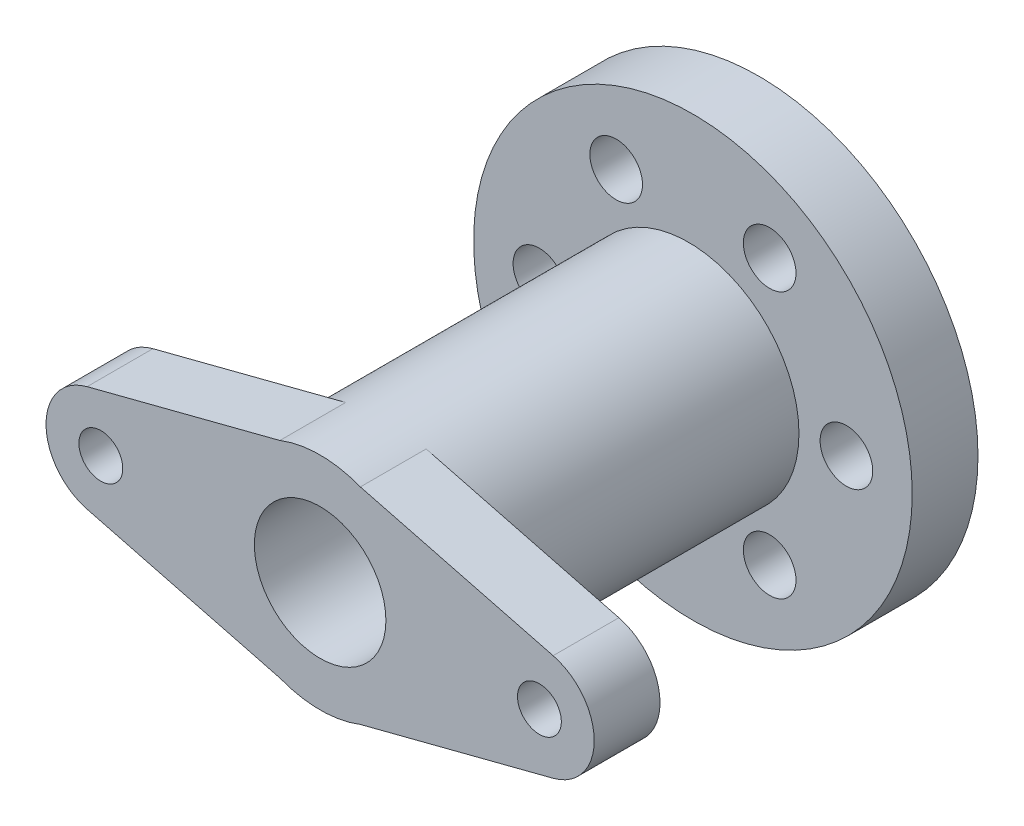
SolidWorks part; units mm, degrees
ref_plane "Front Plane" through (0, 0, 0) normal (0, 0, 1) x (1, 0, 0)
ref_plane "Top Plane" through (0, 0, 0) normal (0, 1, 0) x (1, 0, 0)
ref_plane "Right Plane" through (0, 0, 0) normal (1, 0, 0) x (0, 0, -1)
sketch "Sketch1" plane through (0, 0, 0) normal (0, 0, 1) x (1, 0, 0)
  circle A0 centre (0, 0) radius 50
  circle A1 centre (0, 0) radius 35
  circle A2 centre (-35, 0) radius 6
  circle A3 centre (-17.5, 30.3109) radius 6
  circle A4 centre (0, 0) radius 35
  circle A5 centre (17.5, 30.3109) radius 6
  circle A6 centre (0, 0) radius 35
  circle A7 centre (35, 0) radius 6
  circle A8 centre (0, 0) radius 35
  circle A9 centre (17.5, -30.3109) radius 6
  circle A10 centre (0, 0) radius 35
  circle A11 centre (-17.5, -30.3109) radius 6
  circle A12 centre (0, 0) radius 35
  circle A13 centre (0, 0) radius 15
  point P24 (0, 0)
  dimension "D1" = 100
  dimension "D2" = 70
  dimension "D3" = 12
  dimension "D5" = 30
  dimension "D4" = 6
extrude "Boss-Extrude1" add sketch "Sketch1" along normal blind 15 contours A0 A11 A1 A2 A3 A5 A7 A9 | A11 A1 A9 A7 A5 A3 A2 region at (-48.5858, 0, 0) region at (28.0173, 0, 0)
extrude "Boss-Extrude2" add sketch "Sketch1<3>" along normal blind 85 contours A13 region at (0, 0, 0)
sketch "Sketch1<3>" plane through (0, 0, 0) normal (0, 0, 1) x (1, 0, 0) same geometry as "Sketch1"
sketch "Sketch2" plane through (0, 0, 85) normal (0, 0, 1) x (1, 0, 0)
  line L0 (0, 0) -> (49.3005, 0) construction
  line L1 (-53.125, 12.1031) -> (-6.25, 24.2061)
  line L2 (6.25, 24.2061) -> (53.125, 12.1031)
  line L3 (-53.125, -12.1031) -> (-6.25, -24.2061)
  line L4 (6.25, -24.2061) -> (53.125, -12.1031)
  circle A0 centre (0, 0) radius 15
  arc A1 (-6.25, -24.2061) -> (6.25, -24.2061) centre (0, 0) ccw
  circle A2 centre (-50, 0) radius 5
  circle A3 centre (50, 0) radius 5
  arc A4 (-53.125, 12.1031) -> (-53.125, -12.1031) centre (-50, 0) ccw
  arc A5 (53.125, -12.1031) -> (53.125, 12.1031) centre (50, 0) ccw
  circle A6 centre (0, 0) radius 50 construction
  arc A7 (6.25, 24.2061) -> (-6.25, 24.2061) centre (0, 0) ccw
  dimension "D1" = 30
  dimension "D2" = 50
  dimension "D3" = 10
  dimension "D4" = 25
extrude "Boss-Extrude3" add sketch "Sketch2" along normal blind 15 separate body
sketch "Sketch3" plane through (0, 0, 100) normal (0, 0, 1) x (1, 0, 0)
  circle A0 centre (0, 0) radius 25.1819
extrude "Boss-Extrude4" add sketch "Sketch3" against normal blind 84
sketch "Sketch4" plane through (0, 0, 100) normal (0, 0, 1) x (1, 0, 0)
  circle A0 centre (0, 0) radius 15
extrude "Cut-Extrude1" cut sketch "Sketch4" against normal blind 120
